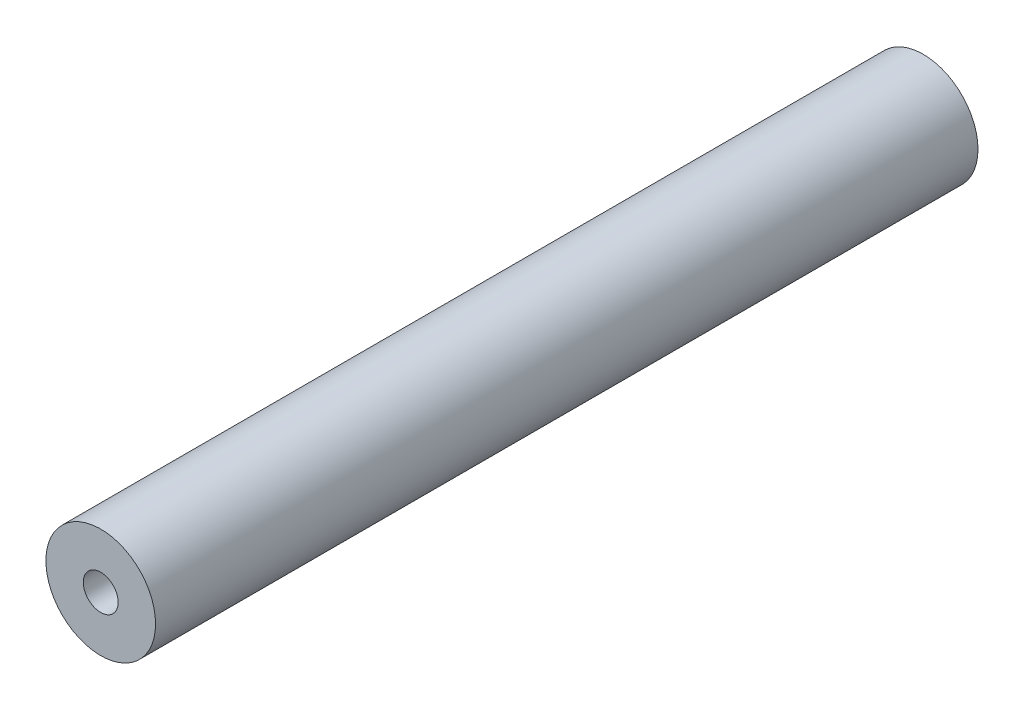
SolidWorks part; units mm, degrees
ref_plane "Front Plane" through (0, 0, 0) normal (0, 0, 1) x (1, 0, 0)
ref_plane "Top Plane" through (0, 0, 0) normal (0, 1, 0) x (1, 0, 0)
ref_plane "Right Plane" through (0, 0, 0) normal (1, 0, 0) x (0, 0, -1)
sketch "Sketch1" plane through (0, 0, 0) normal (0, 0, 1) x (1, 0, 0)
  circle A1 centre (0, 0) radius 6.35
  dimension "D2" = 12.7
extrude "Boss-Extrude1" add sketch "Sketch1" along normal mid plane 95.25 contours A1 region at (0, 0, 0)
hole_wizard "#10-32 Tapped Hole1" positions "3DSketch1" profile "Sketch2" tap size "#10-32" standard "ANSI Inch"
sketch3d "3DSketch1"
  line L0 (0, 0, 47.625) -> (0, 0, -47.625) construction
  point P0 (0, 0, -47.625)
  point P4 (0, 0, 47.625)
sketch "Sketch2" plane through (0, 0, -47.625) normal (1, 0, 0) x (0, 1, 0)
  line L0 (0, 0) -> (0, 13.2428)
  line L1 (0, 13.2428) -> (2.0193, 12.0294)
  line L2 (2.0193, 12.0294) -> (2.0193, 0)
  line L5 (2.0193, 0) -> (0, 0)
  line L10 (0, 13.2428) -> (-2.0193, 12.0294) construction
  line L11 (0, -6.35) -> (0, 107.95) construction
  dimension "Tap Drill Dia." = 4.0386
  dimension "Tap Drill Depth" = 12.0294
  dimension "Drill Angle" = 118
cosmetic thread "Hole Thread1" parameters "D1"=9.652, "D2"=4.826
cosmetic thread "Hole Thread2" parameters "D1"=9.652, "D2"=4.826
